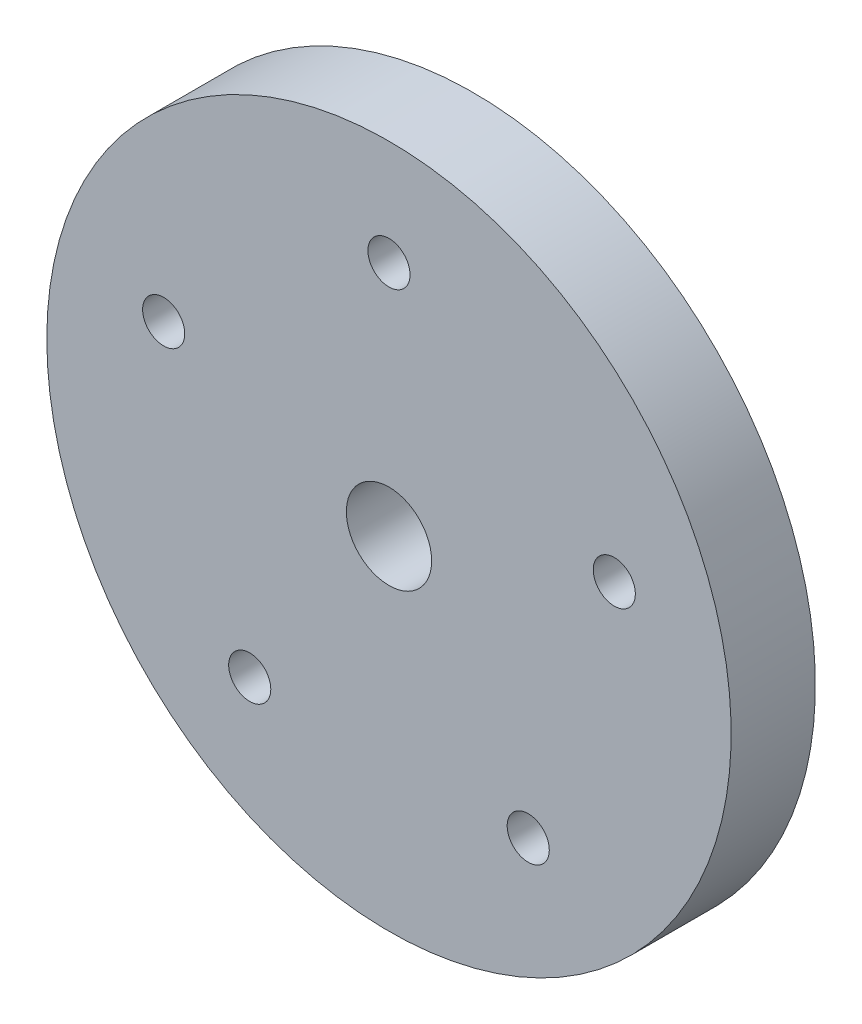
SolidWorks part; units mm, degrees
ref_plane "Ebene vorne" through (0, 0, 0) normal (0, 0, 1) x (1, 0, 0)
ref_plane "Ebene oben" through (0, 0, 0) normal (0, 1, 0) x (1, 0, 0)
ref_plane "Ebene rechts" through (0, 0, 0) normal (1, 0, 0) x (0, 0, -1)
sketch "Skizze1" plane through (0, 0, 0) normal (1, 0, 0) x (0, 0, -1)
  line L0 (0, 0) -> (0, -44862.1348) construction
  line L1 (0, 0) -> (-44862.1348, 0) construction
  line L2 (0, 0) -> (20, 0)
  line L3 (20, 0) -> (20, 15)
  line L4 (20, 15) -> (8, 15)
  line L5 (8, 15) -> (8, 32.5)
  line L6 (8, 32.5) -> (0, 32.5)
  line L7 (0, 32.5) -> (0, 0)
  dimension "D1" = 30
  dimension "D2" = 65
  dimension "D3" = 20
  dimension "D4" = 12
revolve "Rotation1" add sketch "Skizze1" angle 360 about L1
hole_wizard "Ø4.0 (4) Heat Insert M3" positions "Skizze2" profile "Skizze3" hole size "Ø4.0" standard "ISO" end condition through all
sketch "Skizze2" plane through (0, 0, 0) normal (0, 0, 1) x (1, 0, 0)
  circle A0 centre (0, 0) radius 22.5 construction
  point P7 (0, 22.5)
  dimension "D1" = 45
sketch "Skizze3" plane through (0, 22.5, 0) normal (1, 0, 0) x (0, -1, 0)
  line L0 (0, 0) -> (0, 20)
  line L1 (0, 20) -> (2, 20)
  line L2 (2, 20) -> (2, 0)
  line L5 (2, 0) -> (0, 0)
  line L11 (0, -6.35) -> (0, 107.95) construction
  dimension "Bohrerdurchmesser" = 4
  dimension "Bohrungstiefe" = 20
hole_wizard "Ø8.1 (8.1) Durchmesser Bohrung1" positions "Skizze4" profile "Skizze5" hole size "Ø8.1" standard "ISO" end condition through all
sketch "Skizze4" plane through (0, 0, 0) normal (0, 0, 1) x (1, 0, 0)
  point P0 (0, 0)
sketch "Skizze5" plane through (0, 0, 0) normal (1, 0, 0) x (0, -1, 0)
  line L0 (0, 0) -> (0, 20)
  line L1 (0, 20) -> (4.05, 20)
  line L2 (4.05, 20) -> (4.05, 0)
  line L5 (4.05, 0) -> (0, 0)
  line L11 (0, -6.35) -> (0, 107.95) construction
  dimension "Bohrerdurchmesser" = 8.1
  dimension "Bohrungstiefe" = 20
sketch "Skizze8" plane through (0, 0, -20) normal (0, 0, -1) x (-1, 0, 0)
  line L0 (0, 0) -> (0, 50000) construction
  circle A0 centre (0, 0) radius 10 construction
  circle A1 centre (0, 10) radius 1.2
  circle A2 centre (8.6603, -5) radius 1.2
  circle A3 centre (-8.6603, -5) radius 1.2
  point P14 (0, 0)
  dimension "D1" = 20
  dimension "D2" = 2.4
  dimension "D3" = 3
extrude "Schnitt-Linear austragen1" cut sketch "Skizze8" against normal blind 7
pattern_circular "Kreismuster1" count 5 over 360 about axis through (0, 0, 0) along (0, 0, -1) of "Ø4.0 (4) Heat Insert M3"
